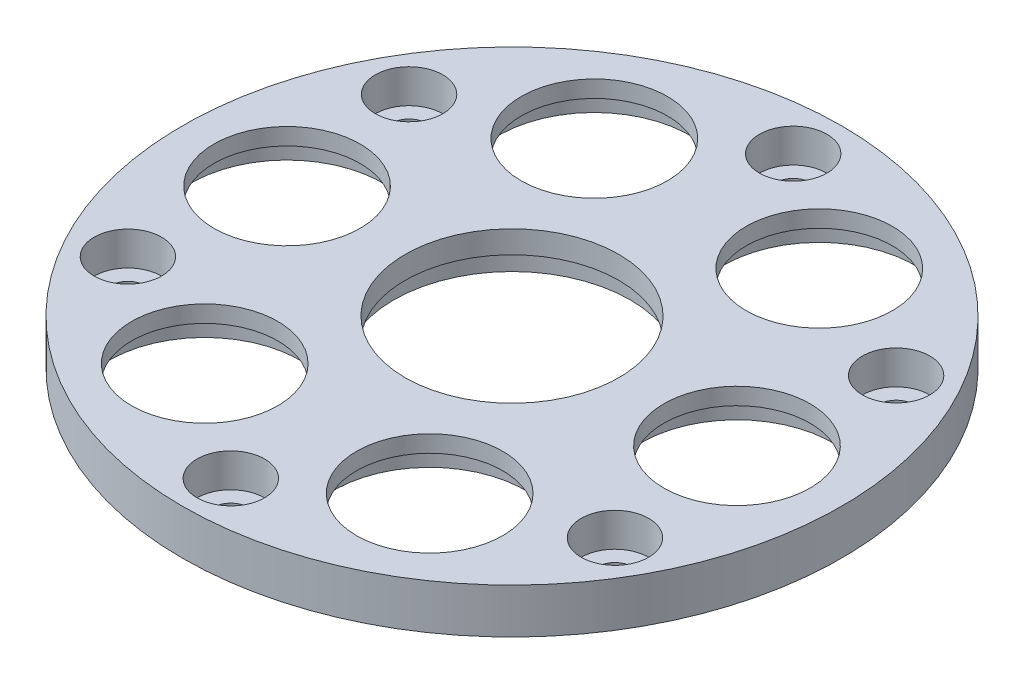
SolidWorks part; units mm, degrees
ref_plane "Front Plane" through (0, 0, 0) normal (0, 0, 1) x (1, 0, 0)
ref_plane "Top Plane" through (0, 0, 0) normal (0, 1, 0) x (1, 0, 0)
ref_plane "Right Plane" through (0, 0, 0) normal (1, 0, 0) x (0, 0, -1)
sketch "Sketch1" plane through (0, 0, 0) normal (0, 1, 0) x (1, 0, 0)
  line L0 (0, 0) -> (-20, 0) construction
  line L1 (-28.5, 0) -> (-29.3, 0) construction
  line L2 (0, 0) -> (0, 25) construction
  circle A0 centre (0, 0) radius 10.5
  circle A1 centre (-20, 0) radius 8.5
  circle A2 centre (0, 0) radius 9.5
  circle A3 centre (-20, 0) radius 6.5
  circle A4 centre (0, 0) radius 29.3
  circle A5 centre (-10, 17.3205) radius 8.5
  circle A6 centre (-10, 17.3205) radius 6.5
  circle A7 centre (10, 17.3205) radius 8.5
  circle A8 centre (10, 17.3205) radius 6.5
  circle A9 centre (20, 0) radius 8.5
  circle A10 centre (20, 0) radius 6.5
  circle A11 centre (10, -17.3205) radius 8.5
  circle A12 centre (10, -17.3205) radius 6.5
  circle A13 centre (-10, -17.3205) radius 8.5
  circle A14 centre (-10, -17.3205) radius 6.5
  circle A15 centre (0, 25) radius 1.55
  circle A16 centre (0, 25) radius 3
  circle A17 centre (21.6506, 12.5) radius 3
  circle A18 centre (21.6506, 12.5) radius 1.55
  circle A19 centre (21.6506, -12.5) radius 3
  circle A20 centre (21.6506, -12.5) radius 1.55
  circle A21 centre (0, -25) radius 3
  circle A22 centre (0, -25) radius 1.55
  circle A23 centre (-21.6506, -12.5) radius 3
  circle A24 centre (-21.6506, -12.5) radius 1.55
  circle A25 centre (-21.6506, 12.5) radius 3
  circle A26 centre (-21.6506, 12.5) radius 1.55
  dimension "D1" = 21
  dimension "D2" = 17
  dimension "D8" = 3.1
  dimension "D9" = 6
  dimension "D3" = 20
  dimension "D4" = 0.8
  dimension "D5" = 2
  dimension "D6" = 1
  dimension "D10" = 25
  dimension "D7" = 6
extrude "Boss-Extrude1" add sketch "Sketch1" against normal blind 4 contours A4
extrude "Cut-Extrude1" cut sketch "Sketch1<4>" against normal through all contours A3 | A14 | A12 | A10 | A8 | A6 | A24 | A22 | A20 | A18 | A15 | A26 | A2 region at (0, 0, 0) region at (-20, 0, 0) region at (-10, 0, -17.3205) region at (10, 0, -17.3205) region at (20, 0, 0) region at (10, 0, 17.3205) region at (-10, 0, 17.3205) region at (0, 0, -25) region at (21.6506, 0, -12.5) region at (21.6506, 0, 12.5) region at (0, 0, 25) region at (-21.6506, 0, 12.5) region at (-21.6506, 0, -12.5)
sketch "Sketch1<4>" plane through (0, 0, 0) normal (0, 1, 0) x (1, 0, 0) same geometry as "Sketch1"
extrude "Cut-Extrude2" cut sketch "Sketch1<5>" against normal through all from offset 1.5 contours A1 A3 | A5 A6 | A7 A8 | A9 A10 | A11 A12 | A13 A14 region at (-28.2596, 0, 0) region at (-18.2596, 0, -17.3205) region at (1.7404, 0, -17.3205) region at (11.7404, 0, 0) region at (1.7404, 0, 17.3205) region at (-18.2596, 0, 17.3205) offset against normal yes
sketch "Sketch1<5>" plane through (0, 0, 0) normal (0, 1, 0) x (1, 0, 0) same geometry as "Sketch1"
extrude "Cut-Extrude3" cut sketch "Sketch1<6>" against normal through all from offset 2 contours A0 A2 region at (-10.203, 0, 0) offset against normal yes
sketch "Sketch1<6>" plane through (0, 0, 0) normal (0, 1, 0) x (1, 0, 0) same geometry as "Sketch1"
extrude "Cut-Extrude4" cut sketch "Sketch1<7>" against normal blind 3 contours A25 A26 | A16 A15 | A17 A18 | A19 A20 | A21 A22 | A23 A24 region at (-2.9151, 0, -25) region at (18.7355, 0, -12.5) region at (18.7355, 0, 12.5) region at (-2.9151, 0, 25) region at (-24.5658, 0, 12.5) region at (-24.5658, 0, -12.5)
sketch "Sketch1<7>" plane through (0, 0, 0) normal (0, 1, 0) x (1, 0, 0) same geometry as "Sketch1"
equation "\"Ratio\"= 15"
equation "\"Hull Diameter\"= 3.5in"
equation "\"Fixed Ring Diameter\"= 76"
equation "\"Fixed Pin Diameter\"= 6"
equation "\"Output Ring Diameter\"= 40"
equation "\"Output Pin Diameter\"= 6"
equation "\"Disk Bearing Inner Diameter\"= 9"
equation "\"Disk Bearing Outer Diameter\"= 17"
equation "\"Disk Bearing Height\"= 5"
equation "\"Shaft Bearing Inner Diameter\"= 15"
equation "\"Shaft Bearing Outer Diameter\"= 21"
equation "\"Shaft Bearing Height\"= 4"
equation "\"Eccentricity\"= 1.5"
equation "\"Disk Height\"= 8"
equation "\"Disk Spacing\"= 5"
equation "\"Hull Height\"= 40"
equation "\"Shaft End Bearing Inner Diameter\"= 12"
equation "\"Shaft End Bearing Outer Diameter\"= 18"
equation "\"Shaft End Bearing Height\"= 4"
equation "\"Output Bearing Inner Diameter\"= 55"
equation "\"Output Bearing Outer Diameter\"= 72"
equation "\"Outer Bearing Height\"= 9"
equation "\"D1@Sketch1\"=\"Shaft Bearing Outer Diameter\""
equation "\"D2@Sketch1\"=\"Disk Bearing Outer Diameter\""
equation "\"D3@Sketch1\"=\"Output Ring Diameter\"/2"
